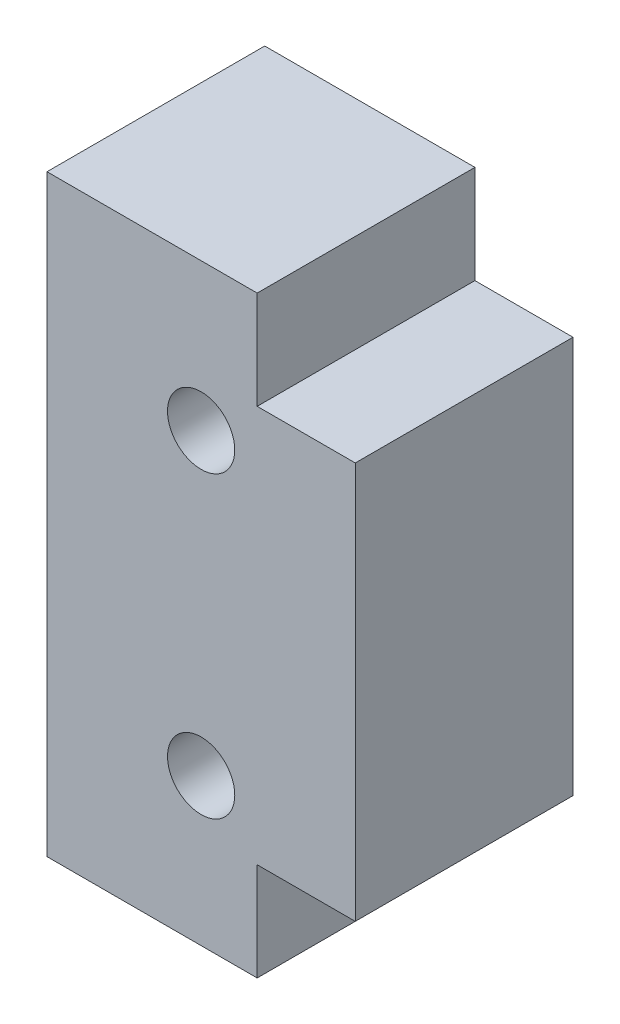
SolidWorks part; units mm, degrees
ref_plane "Front Plane" through (0, 0, 0) normal (0, 0, 1) x (1, 0, 0)
ref_plane "Top Plane" through (0, 0, 0) normal (0, 1, 0) x (1, 0, 0)
ref_plane "Right Plane" through (0, 0, 0) normal (1, 0, 0) x (0, 0, -1)
sketch "Sketch2" plane through (0, 0, 0) normal (0, 0, 1) x (1, 0, 0)
  line L0 (8.25, -152.4) -> (8.25, 152.4) construction
  line L1 (8.25, -39.1052) -> (-8.25, -39.1052)
  line L2 (8.25, -39.1052) -> (8.25, -7.3552)
  line L3 (8.25, -7.3552) -> (-8.25, -7.3552)
  line L4 (-8.25, -39.1052) -> (-8.25, -7.3552)
  line L5 (-8.25, -152.4) -> (-8.25, 152.4) construction
extrude "Boss-Extrude1" add sketch "Sketch2" along normal up to surface (11.655 mm away)
sketch "Sketch3" plane through (0, 0, 11.655) normal (0, 0, 1) x (1, 0, 0)
  line L0 (3.6, -31.2302) -> (3.6, -15.2302) construction
  line L1 (3.6, -34.8302) -> (-3.6, -34.8302)
  line L2 (3.6, -34.8302) -> (3.6, -11.6302)
  line L3 (3.6, -11.6302) -> (-3.6, -11.6302)
  line L4 (-3.6, -34.8302) -> (-3.6, -11.6302)
  line L5 (-4.4, -34.8302) -> (0, -34.8302) construction
  line L6 (0, -11.6302) -> (-4.4, -11.6302) construction
  circle A0 centre (0, -31.2302) radius 2.4 construction
  dimension "D1" = 3.6
extrude "Boss-Extrude2" [suppressed] add sketch "Sketch3" along normal up to surface (6 mm away)
sketch "Sketch4" [suppressed] plane through (0, 0, 11.81) normal (0, 0, 1) x (1, 0, 0)
  circle A4 centre (0, -31.2302) radius 2.8
  circle A5 centre (0, -15.2302) radius 2.8
extrude "Cut-Extrude1" [suppressed] cut sketch "Sketch4" against normal through all
sketch "Sketch5" plane through (0, 0, 11.655) normal (0, 0, 1) x (1, 0, 0)
  line L0 (3, -152.4) -> (3, 152.4) construction
  line L1 (8.25, -39.1052) -> (3, -39.1052)
  line L2 (8.25, -39.1052) -> (8.25, -33.8552)
  line L3 (8.25, -33.8552) -> (3, -33.8552)
  line L4 (3, -39.1052) -> (3, -33.8552)
  line L5 (8.25, -7.3552) -> (3, -7.3552)
  line L6 (8.25, -7.3552) -> (8.25, -12.6052)
  line L7 (8.25, -12.6052) -> (3, -12.6052)
  line L8 (3, -7.3552) -> (3, -12.6052)
extrude "Cut-Extrude2" cut sketch "Sketch5" against normal through all
sketch "Sketch6" plane through (0, 0, 11.655) normal (0, 0, 1) x (1, 0, 0)
  circle A0 centre (0, -15.2302) radius 2.4 construction
  circle A1 centre (0, -31.2302) radius 2.4 construction
  circle A2 centre (0, -15.2302) radius 2.4 construction
  circle A3 centre (0, -31.2302) radius 2.4 construction
  circle A4 centre (0, -31.2302) radius 1.8
  circle A5 centre (0, -15.2302) radius 1.8
  dimension "D1" = 0.6
extrude "Cut-Extrude3" cut sketch "Sketch6" against normal through all
